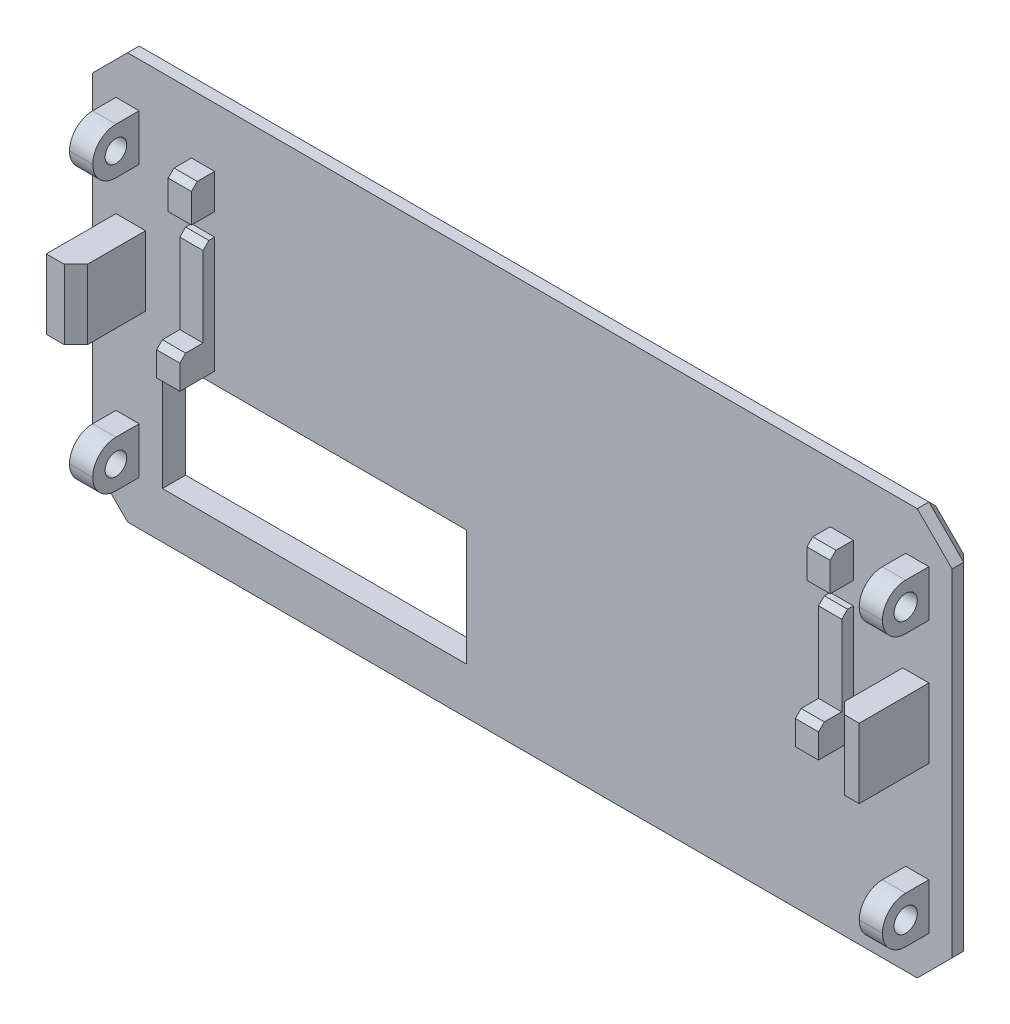
SolidWorks part; units mm, degrees
ref_plane "前视基准面" through (0, 0, 0) normal (0, 0, 1) x (1, 0, 0)
ref_plane "上视基准面" through (0, 0, 0) normal (0, 1, 0) x (1, 0, 0)
ref_plane "右视基准面" through (0, 0, 0) normal (1, 0, 0) x (0, 0, -1)
other "Configuration Table"
sketch "草图1" plane through (0, 0, 0) normal (0, 0, 1) x (1, 0, 0)
  line L0 (-39.7638, 14.7992) -> (-36.7638, 17.7992)
  line L5 (-36.7638, 17.7992) -> (31.2362, 17.7992)
  line L6 (-39.7638, 14.7992) -> (-39.7638, -14.2008)
  line L7 (-36.7638, -17.2008) -> (31.2362, -17.2008)
  line L8 (34.2362, 14.7992) -> (34.2362, -14.2008)
  line L9 (-39.7638, -14.2008) -> (-36.7638, -17.2008)
  line L10 (31.2362, -17.2008) -> (34.2362, -14.2008)
  line L11 (31.2362, 17.7992) -> (34.2362, 14.7992)
  point P0 (-39.7638, 17.7992)
  point P1 (34.2362, -17.2008)
  point P2 (-39.7638, -17.2008)
  point P3 (34.2362, 17.7992)
  dimension "D1" = 74
  dimension "D2" = 35
extrude "凸台-拉伸1" add sketch "草图1" along normal blind 2
chamfer "倒角1" distance 1 angle 45 8 edges at (-38.2638, 16.2992, 0) (-2.7638, -17.2008, 0) (-39.7638, 0.2992, 0) (-38.2638, -15.7008, 0) (32.7362, -15.7008, 0) (34.2362, 0.2992, 0) (32.7362, 16.2992, 0) (-2.7638, 17.7992, 0)
sketch "草图3" plane through (0, 0, 2) normal (0, 0, 1) x (1, 0, 0)
  line L1 (-37.7638, 13.9708) -> (-35.7638, 13.9708)
  line L2 (-37.7638, 13.9708) -> (-37.7638, 9.9708)
  line L3 (-37.7638, 9.9708) -> (-35.7638, 9.9708)
  line L4 (-35.7638, 13.9708) -> (-35.7638, 9.9708)
  line L5 (-37.7638, -13.3724) -> (-35.7638, -13.3724)
  line L6 (-37.7638, -13.3724) -> (-37.7638, -9.3724)
  line L7 (-37.7638, -9.3724) -> (-35.7638, -9.3724)
  line L8 (-35.7638, -13.3724) -> (-35.7638, -9.3724)
  line L9 (32.2362, 13.9708) -> (30.2362, 13.9708)
  line L10 (32.2362, 13.9708) -> (32.2362, 9.9708)
  line L11 (32.2362, 9.9708) -> (30.2362, 9.9708)
  line L12 (30.2362, 13.9708) -> (30.2362, 9.9708)
  line L13 (32.2362, -13.3724) -> (30.2362, -13.3724)
  line L14 (32.2362, -13.3724) -> (32.2362, -9.3724)
  line L15 (32.2362, -9.3724) -> (30.2362, -9.3724)
  line L16 (30.2362, -13.3724) -> (30.2362, -9.3724)
  dimension "D1" = 2
  dimension "D2" = 4
extrude "凸台-拉伸2" add sketch "草图3" along normal blind 4
fillet "圆角1" radius 2 8 edges at (31.2362, 13.9708, 6) (31.2362, 9.9708, 6) (31.2362, -9.3724, 6) (31.2362, -13.3724, 6) (-36.7638, -13.3724, 6) (-36.7638, -9.3724, 6) (-36.7638, 13.9708, 6) (-36.7638, 9.9708, 6)
sketch "草图4" plane through (32.2362, 0, 0) normal (1, 0, 0) x (0, 0, -1)
  circle A0 centre (-4, 11.9708) radius 1
  circle A1 centre (-4, -11.3724) radius 1
  dimension "D1" = 2
extrude "切除-拉伸1" cut sketch "草图4" against normal up to next (2 mm away) draft 2
sketch "草图5" plane through (-37.7638, 0, 0) normal (-1, 0, 0) x (0, 0, 1)
  circle A0 centre (4, 11.9708) radius 1
  circle A1 centre (4, -11.3724) radius 1
  dimension "D1" = 2
extrude "切除-拉伸2" cut sketch "草图5" against normal up to next (2 mm away) draft 2
sketch "草图6" plane through (0, 0, 2) normal (0, 0, 1) x (1, 0, 0)
  line L0 (31.2362, 17.7992) -> (-36.7638, 17.7992) construction
  line L1 (-31.2638, 7.7992) -> (-29.2638, 7.7992)
  line L2 (-31.2638, 7.7992) -> (-31.2638, -2.2008)
  line L3 (-31.2638, -2.2008) -> (-29.2638, -2.2008)
  line L4 (-29.2638, 7.7992) -> (-29.2638, -2.2008)
  line L5 (23.7362, 7.7992) -> (25.7362, 7.7992)
  line L6 (23.7362, 7.7992) -> (23.7362, -2.2008)
  line L7 (23.7362, -2.2008) -> (25.7362, -2.2008)
  line L8 (25.7362, 7.7992) -> (25.7362, -2.2008)
  line L9 (-39.7638, 14.7992) -> (-39.7638, -14.2008) construction
  line L10 (34.2362, -14.2008) -> (34.2362, 14.7992) construction
  dimension "D1" = 10
  dimension "D2" = 10
  dimension "D3" = 8.5
  dimension "D4" = 8.5
  dimension "D5" = 10
  dimension "D6" = 2
extrude "凸台-拉伸3" add sketch "草图6" along normal blind 1
sketch "草图7" plane through (0, 0, 3) normal (0, 0, 1) x (1, 0, 0)
  line L0 (-29.2638, -2.2008) -> (-29.2638, 7.7992) construction
  line L1 (-31.2638, -2.2008) -> (-29.2638, -2.2008)
  line L2 (-31.2638, -2.2008) -> (-31.2638, 0.3992)
  line L3 (-31.2638, 0.3992) -> (-29.2638, 0.3992)
  line L4 (-29.2638, -2.2008) -> (-29.2638, 0.3992)
  line L5 (25.7362, -2.2008) -> (25.7362, 7.7992) construction
  line L6 (23.7362, -2.2008) -> (25.7362, -2.2008)
  line L7 (23.7362, -2.2008) -> (23.7362, 0.3992)
  line L8 (23.7362, 0.3992) -> (25.7362, 0.3992)
  line L9 (25.7362, -2.2008) -> (25.7362, 0.3992)
  point P14 (0, 0)
  dimension "D1" = 2.6
extrude "凸台-拉伸4" add sketch "草图7" along normal blind 2
chamfer "倒角2" distance 0.5 angle 45 4 edges at (24.7362, 7.7992, 3) (24.7362, 0.3992, 5) (-30.2638, 7.7992, 3) (-30.2638, 0.3992, 5)
sketch "草图8" plane through (0, 0, 2) normal (0, 0, 1) x (1, 0, 0)
  line L0 (-37.7638, 13.9708) -> (-37.7638, -13.3724) construction
  line L1 (-37.7638, 5.2992) -> (-35.2138, 5.2992)
  line L2 (-37.7638, 5.2992) -> (-37.7638, -0.7008)
  line L3 (-37.7638, -0.7008) -> (-35.2138, -0.7008)
  line L4 (-35.2138, 5.2992) -> (-35.2138, -0.7008)
  line L5 (31.2362, 17.7992) -> (-36.7638, 17.7992) construction
  line L6 (32.2362, -13.3724) -> (32.2362, 13.9708) construction
  line L7 (32.2362, 5.2992) -> (29.9862, 5.2992)
  line L8 (32.2362, 5.2992) -> (32.2362, -0.7008)
  line L9 (32.2362, -0.7008) -> (29.9862, -0.7008)
  line L10 (29.9862, 5.2992) -> (29.9862, -0.7008)
  point P14 (0, 0)
  point P15 (0, 0)
  dimension "D1" = 12.5
  dimension "D2" = 6
  dimension "D3" = 2.55
  dimension "D4" = 2.25
extrude "凸台-拉伸5" add sketch "草图8" along normal blind 6
chamfer "倒角3" distance 1 angle 45 2 edges at (29.9862, 2.2992, 8) (-35.2138, 2.2992, 8)
sketch "草图9" plane through (0, 0, 2) normal (0, 0, 1) x (1, 0, 0)
  line L0 (31.2362, 17.7992) -> (-36.7638, 17.7992) construction
  line L1 (-31.2638, 12.6992) -> (-29.2638, 12.6992)
  line L2 (-31.2638, 12.6992) -> (-31.2638, 9.6992)
  line L3 (-31.2638, 9.6992) -> (-29.2638, 9.6992)
  line L4 (-29.2638, 12.6992) -> (-29.2638, 9.6992)
  line L5 (23.7362, 12.6992) -> (25.7362, 12.6992)
  line L6 (23.7362, 12.6992) -> (23.7362, 9.6992)
  line L7 (23.7362, 9.6992) -> (25.7362, 9.6992)
  line L8 (25.7362, 12.6992) -> (25.7362, 9.6992)
  line L9 (34.2362, -14.2008) -> (34.2362, 14.7992) construction
  line L10 (-39.7638, 14.7992) -> (-39.7638, -14.2008) construction
  point P12 (0, 0)
  dimension "D1" = 5.1
  dimension "D2" = 8.5
  dimension "D3" = 2
  dimension "D4" = 3
  dimension "D5" = 8.5
extrude "凸台-拉伸6" add sketch "草图9" along normal blind 2
chamfer "倒角4" distance 0.5 angle 45 2 edges at (24.7362, 12.6992, 4) (-30.2638, 12.6992, 4)
sketch "草图10" plane through (0, 0, 0) normal (0, 0, -1) x (-1, 0, 0)
  line L0 (36.7638, -17.2008) -> (-31.2362, -17.2008) construction
  line L1 (7.5638, -3.2008) -> (33.7638, -3.2008)
  line L2 (7.5638, -3.2008) -> (7.5638, -13.2008)
  line L3 (7.5638, -13.2008) -> (33.7638, -13.2008)
  line L4 (33.7638, -3.2008) -> (33.7638, -13.2008)
  line L5 (39.7638, 14.7992) -> (39.7638, -14.2008) construction
  dimension "D1" = 4
  dimension "D2" = 10
  dimension "D3" = 6
  dimension "D4" = 26.2
extrude "切除-拉伸3" cut sketch "草图10" against normal up to next
